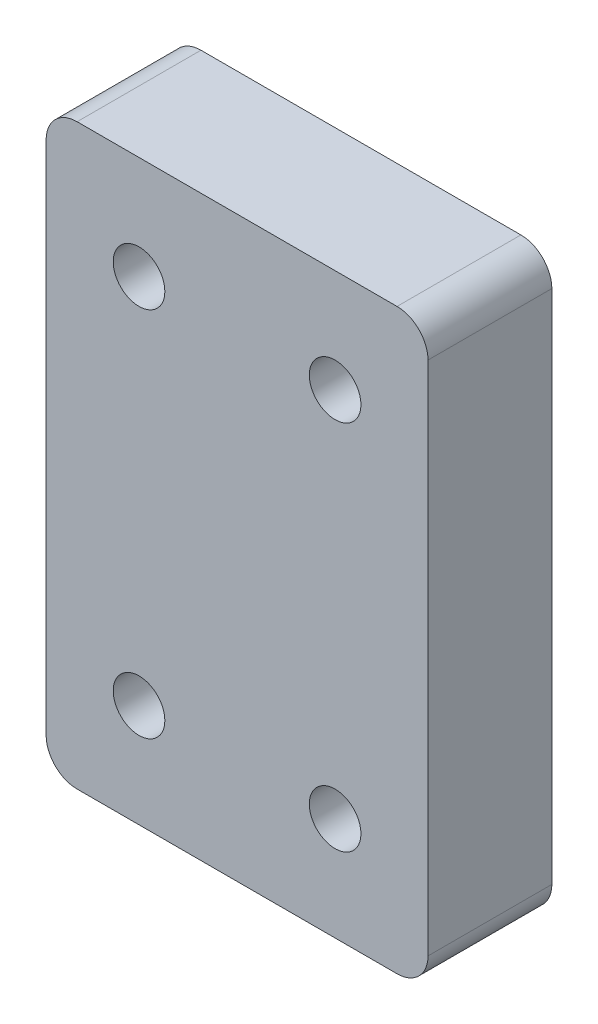
SolidWorks part; units mm, degrees
material "Maple"
ref_plane "Front" through (0, 0, 0) normal (0, 0, 1) x (1, 0, 0)
ref_plane "Top" through (0, 0, 0) normal (0, 1, 0) x (1, 0, 0)
ref_plane "Right" through (0, 0, 0) normal (1, 0, 0) x (0, 0, -1)
sketch "Sketch1" plane through (0, 0, 0) normal (0, 0, 1) x (1, 0, 0)
  line L5 (-15.5, -28) -> (15.5, -28)
  line L6 (-18.5, -25) -> (-18.5, 25)
  line L7 (-15.5, 28) -> (15.5, 28)
  line L8 (18.5, -25) -> (18.5, 25)
  line L9 (-18.5, -28) -> (18.5, 28) construction
  line L10 (-18.5, 28) -> (18.5, -28) construction
  arc A4 (-15.5, -28) -> (-18.5, -25) centre (-15.5, -25) cw
  arc A5 (15.5, -28) -> (18.5, -25) centre (15.5, -25) ccw
  arc A6 (15.5, 28) -> (18.5, 25) centre (15.5, 25) cw
  arc A7 (-18.5, 25) -> (-15.5, 28) centre (-15.5, 25) cw
  point P0 (0, 0)
  dimension "D3" = 3
  dimension "D1" = 37
  dimension "D2" = 56
extrude "Boss-Extrude1" add sketch "Sketch1" along normal blind 12
sketch "Sketch2" plane through (0, 0, 12) normal (0, 0, 1) x (1, 0, 0)
  line L0 (-43.0827, 0) -> (40.1391, 0) construction
  line L6 (-18.5, 25) -> (-18.5, -25) construction
  line L7 (0, 31.8162) -> (0, -46.8362) construction
  circle A0 centre (-9.5, 18) radius 2.5
  circle A1 centre (-9.5, -18) radius 2.5
  circle A2 centre (9.5, -18) radius 2.5
  circle A3 centre (9.5, 18) radius 2.5
  point P0 (0, 0)
  dimension "D3" = 5
  dimension "D1" = 9
  dimension "D4" = 36
extrude "Cut-Extrude1" cut sketch "Sketch2" against normal blind 4
